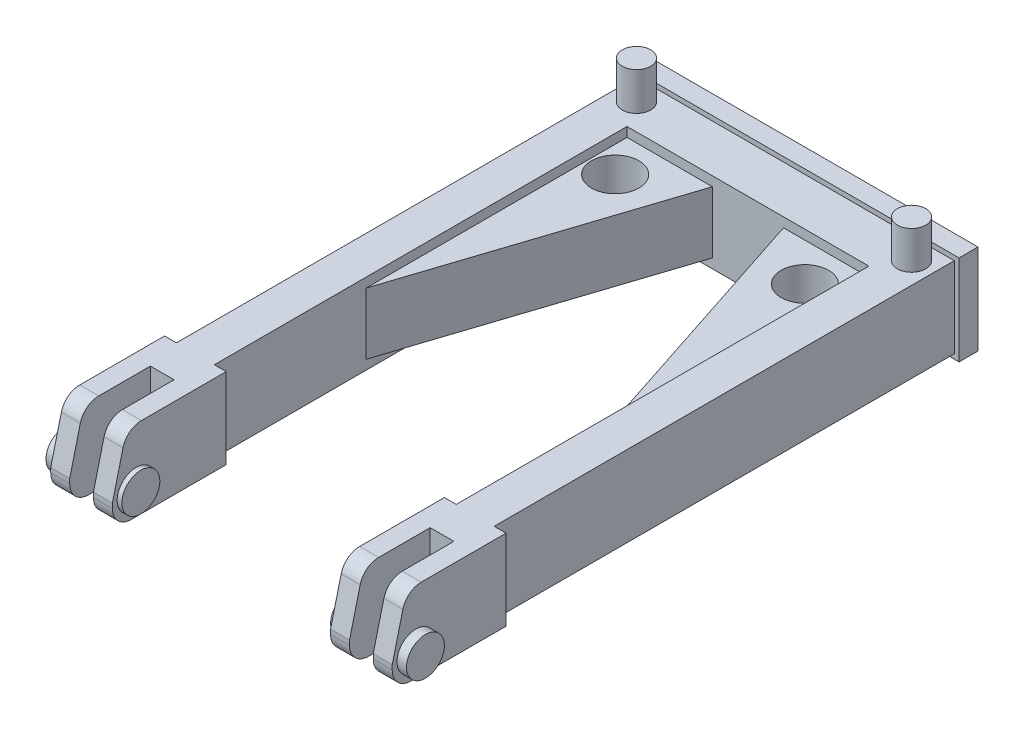
SolidWorks part; units mm, degrees
ref_plane "Front Plane" through (0, 0, 0) normal (0, 0, 1) x (1, 0, 0)
ref_plane "Top Plane" through (0, 0, 0) normal (0, 1, 0) x (1, 0, 0)
ref_plane "Right Plane" through (0, 0, 0) normal (1, 0, 0) x (0, 0, -1)
sketch "Sketch1" plane through (0, 0, 0) normal (0, 1, 0) x (1, 0, 0)
  line L0 (0, 0) -> (0, 8.7) construction
  line L1 (-3.35, 0) -> (-2.55, 0) construction
  line L2 (-3.35, 0) -> (-3.35, 10.1)
  line L3 (-3.35, 10.1) -> (3.35, 10.1)
  line L4 (3.35, 0) -> (3.35, 10.1)
  line L5 (-3.35, 0) -> (-3.6, 0)
  line L6 (-3.6, 0) -> (-3.6, -2.4)
  line L7 (-3.6, -2.4) -> (-2.3, -2.4)
  line L8 (2.55, 0) -> (3.35, 0) construction
  line L9 (-2.55, 0) -> (-2.55, 8.7)
  line L10 (2.55, 0) -> (2.55, 8.7)
  line L11 (-2.55, 8.7) -> (2.55, 8.7)
  line L12 (-2.3, -2.4) -> (-2.3, 0)
  line L13 (-2.3, 0) -> (-2.55, 0)
  line L14 (2.55, 0) -> (2.3, 0)
  line L15 (2.3, 0) -> (2.3, -2.4)
  line L16 (2.3, -2.4) -> (3.6, -2.4)
  line L17 (3.6, -2.4) -> (3.6, 0)
  line L18 (3.6, 0) -> (3.35, 0)
  dimension "D1" = 1.4
  dimension "D2" = 6.7
  dimension "D3" = 0.8
  dimension "D4" = 0.8
  dimension "D5" = 0.25
  dimension "D6" = 2.4
  dimension "D7" = 12.5
extrude "Boss-Extrude1" add sketch "Sketch1" along normal mid plane 1.7
sketch "Sketch3" plane through (0, 0, 0) normal (0, 1, 0) x (1, 0, 0)
  line L0 (-0.75, 8.7) -> (-2.55, 8.7)
  line L1 (-2.55, 8.7) -> (2.55, 8.7) construction
  line L2 (-2.55, 8.7) -> (-2.55, 3.2)
  line L3 (-2.55, 0) -> (-2.55, 8.7) construction
  line L4 (-2.55, 3.2) -> (-0.75, 8.7)
  line L7 (0, 0) -> (0, 13.4734) construction
  line L8 (2.55, 3.2) -> (0.75, 8.7)
  line L9 (2.55, 8.7) -> (2.55, 3.2)
  line L10 (0.75, 8.7) -> (2.55, 8.7)
  circle A0 centre (-2, 7.9) radius 0.5
  circle A1 centre (2, 7.9) radius 0.5
  dimension "D1" = 1
  dimension "D2" = 0.8
  dimension "D3" = 0.55
  dimension "D4" = 1.8
  dimension "D5" = 5.5
extrude "Boss-Extrude2" add sketch "Sketch3" along normal mid plane 1.3
sketch "Sketch4" plane through (0, 0, -10.1) normal (0, 0, -1) x (-1, 0, 0)
  line L8 (-3.45, -0.95) -> (3.45, -0.95)
  line L9 (3.45, -0.95) -> (3.45, 0.95)
  line L10 (3.45, 0.95) -> (-3.45, 0.95)
  line L11 (-3.45, 0.95) -> (-3.45, -0.95)
  line L12 (-3.45, -0.95) -> (3.45, -0.95)
  line L13 (3.45, -0.95) -> (3.45, 0.95)
  line L14 (3.45, 0.95) -> (-3.45, 0.95)
  line L15 (-3.45, 0.95) -> (-3.45, -0.95)
  dimension "D1" = 0.1
extrude "Boss-Extrude3" add sketch "Sketch4" against normal blind 0.4
fillet "Fillet1" radius 0.4 2 edges at (2.95, -0.85, 2.4) (-2.95, -0.85, 2.4)
chamfer "Chamfer1" distance 1.2 distance2 0.3 2 edges at (2.95, 0.85, 2.4) (-2.95, 0.85, 2.4) first distance on face at (2.95, 0.2, 2.4) first distance on face at (-2.95, 0.2, 2.4)
fillet "Fillet2" radius 0.4 2 edges at (2.95, 0.85, 2.1) (-2.95, 0.85, 2.1)
sketch "Sketch7" plane through (-3.6, 0, 0) normal (-1, 0, 0) x (0, 0, 1)
  line L0 (2.4, -0.35) -> (2.4, -0.45) construction
  line L2 (0, -0.85) -> (2, -0.85) construction
  circle A0 centre (1.9, -0.35) radius 0.5 construction
  circle A1 centre (1.9, -0.35) radius 0.4
  dimension "D1" = 1
  dimension "D2" = 0.8
extrude "Boss-Extrude4" add sketch "Sketch7" along normal blind 0.2 and the other way blind 1.4
sketch "Sketch8" plane through (3.6, 0, 0) normal (1, 0, 0) x (0, 0, -1)
  circle A1 centre (-1.9, -0.35) radius 0.4
  circle A2 centre (-1.9, -0.35) radius 0.4
  dimension "D1" = 0
extrude "Boss-Extrude5" add sketch "Sketch8" along normal blind 0.2 and the other way blind 1.4
sketch "Sketch6" plane through (0, 0.85, 0) normal (0, 1, 0) x (1, 0, 0)
  line L0 (-2.3, -2.4) -> (-3.6, -2.4) construction
  line L1 (-3.2, -0.7) -> (-2.7, -0.7)
  line L2 (-3.2, -0.7) -> (-3.2, -2.4)
  line L3 (-3.2, -2.4) -> (-2.7, -2.4)
  line L4 (-2.7, -0.7) -> (-2.7, -2.4)
  line L6 (2.7, -0.7) -> (2.7, -2.4)
  line L7 (3.2, -2.4) -> (2.7, -2.4)
  line L8 (3.2, -0.7) -> (3.2, -2.4)
  line L9 (3.2, -0.7) -> (2.7, -0.7)
  line L10 (-3.35, 0) -> (-3.6, 0) construction
  line L11 (-3.6, 0) -> (-3.6, -1.7877) construction
  line L12 (-2.3, -1.7877) -> (-2.3, 0) construction
  line L13 (0, 0) -> (0, 1.2086) construction
  dimension "D1" = 0.7
  dimension "D2" = 0.4
  dimension "D3" = 0.4
extrude "Cut-Extrude1" cut sketch "Sketch6" against normal through all
sketch "Sketch9" plane through (0, -0.85, 0) normal (0, -1, 0) x (1, 0, 0)
  line L0 (-3.35, -9.7) -> (-3.35, 0) construction
  line L1 (3.45, -9.7) -> (-3.45, -9.7) construction
  line L2 (0, -9.7) -> (0, -7.7112) construction
  line L3 (3.35, -9.7) -> (-3.35, -9.7) construction
  circle A0 centre (-2.9, -9.25) radius 0.35
  circle A1 centre (2.9, -9.25) radius 0.35
  dimension "D1" = 0.7
  dimension "D2" = 0.45
  dimension "D3" = 0.45
extrude "Boss-Extrude6" add sketch "Sketch9" along normal blind 0.1
sketch "Sketch10" plane through (0, 0.85, 0) normal (0, 1, 0) x (1, 0, 0)
  circle A0 centre (-2.9, 9.25) radius 0.3
  circle A1 centre (2.9, 9.25) radius 0.3
  dimension "D1" = 0.6
extrude "Boss-Extrude7" add sketch "Sketch10" along normal blind 0.8
scale "Scale1" scale about origin uniform scaling yes scale factor 2
sketch "Sketch11" plane through (-7.2, 0, 0) normal (-1, 0, 0) x (0, 0, 1)
  line L0 (0, -1.7) -> (4, -1.7) construction
  line L1 (0, 1.7) -> (3.5754, 1.7) construction
  line L2 (4.8, -0.7) -> (4.3515, 1.094) construction
  circle A0 centre (2.8727, 0) radius 1.7
ref_axis "Axis1" through (-7.2, 0, 2.8727) along (-1, 0, 0)
